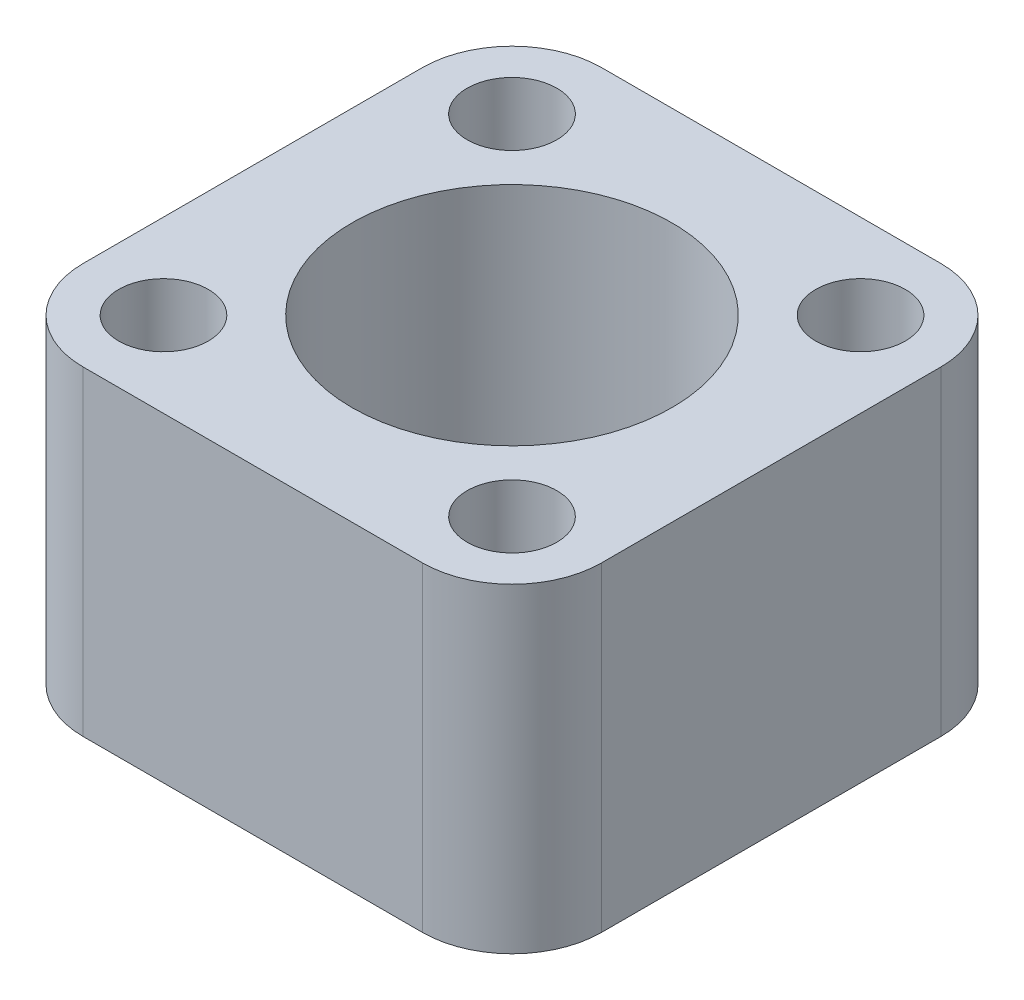
SolidWorks part; units mm, degrees
material "6061-T6 (SS)"
ref_plane "Front Plane" through (0, 0, 0) normal (0, 0, 1) x (1, 0, 0)
ref_plane "Top Plane" through (0, 0, 0) normal (0, 1, 0) x (1, 0, 0)
ref_plane "Right Plane" through (0, 0, 0) normal (1, 0, 0) x (0, 0, -1)
sketch "Sketch3" plane through (0, 0, 0) normal (0, 1, 0) x (1, 0, 0)
  line L1 (0, 0) -> (-20.574, 0)
  line L2 (0, 0) -> (0, 20.574)
  line L3 (0, 20.574) -> (-20.574, 20.574)
  line L4 (-20.574, 0) -> (-20.574, 20.574)
  dimension "D1" = 20.574
extrude "Boss-Extrude2" add sketch "Sketch3" along normal blind 12.7 contours L3 L4 L1 L2
fillet "Fillet2" radius 3.556 4 edges at (-20.574, 6.35, 0) (0, 6.35, 0) (0, 6.35, -20.574) (-20.574, 6.35, -20.574)
sketch "Sketch4" plane through (0, 12.7, 0) normal (0, 1, 0) x (1, 0, 0)
  line L0 (-10.287, 0) -> (-10.287, 20.574) construction
  line L1 (-3.556, 0) -> (-17.018, 0) construction
  line L2 (-3.556, 20.574) -> (-17.018, 20.574) construction
  line L3 (0, 10.287) -> (-20.574, 10.287) construction
  line L4 (0, 3.556) -> (0, 17.018) construction
  line L5 (-20.574, 3.556) -> (-20.574, 17.018) construction
  line L6 (-10.287, 10.287) -> (-3.3722, 3.3722) construction
  line L7 (-10.287, 10.287) -> (-17.2018, 3.3722) construction
  line L8 (-10.287, 10.287) -> (-3.3722, 17.2018) construction
  line L9 (-10.287, 10.287) -> (-17.2018, 17.2018) construction
  circle A0 centre (-10.287, 10.287) radius 6.35
  circle A1 centre (-3.3722, 3.3722) radius 1.778
  circle A2 centre (-17.2018, 3.3722) radius 1.778
  circle A3 centre (-17.2018, 17.2018) radius 1.778
  circle A4 centre (-3.3722, 17.2018) radius 1.778
  dimension "D1" = 12.7
  dimension "D2" = 9.779
  dimension "D3" = 3.556
extrude "Cut-Extrude1" cut sketch "Sketch4" against normal up to surface (12.7 mm away) up to face at (-10.287, 0, -10.287)
